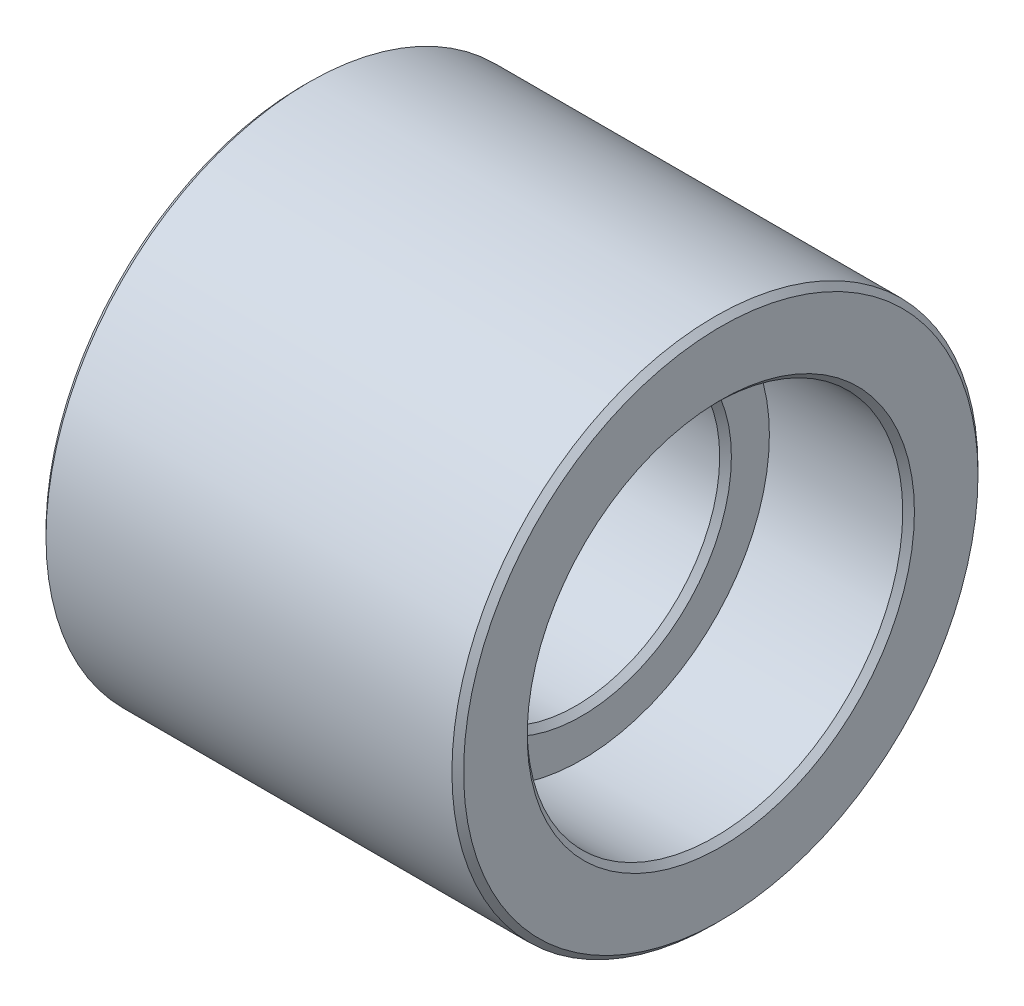
SolidWorks part; units mm, degrees
ref_plane "Front Plane" through (0, 0, 0) normal (0, 0, 1) x (1, 0, 0)
ref_plane "Top Plane" through (0, 0, 0) normal (0, 1, 0) x (1, 0, 0)
ref_plane "Right Plane" through (0, 0, 0) normal (1, 0, 0) x (0, 0, -1)
sketch "Sketch1" plane through (0, 0, 0) normal (0, 1, 0) x (1, 0, 0)
  line L0 (0, 9) -> (0, -9) construction
  line L1 (-7.1438, 9) -> (7.1438, 9)
  line L2 (7.1438, 9) -> (7.1438, 6.425)
  line L3 (7.1438, 6.425) -> (2.3813, 6.425)
  line L4 (2.3813, 6.425) -> (2.3813, 4.925)
  line L5 (2.3813, -6.425) -> (7.1438, -6.425)
  line L6 (7.1438, -6.425) -> (7.1438, -9)
  line L7 (7.1438, -9) -> (-7.1438, -9)
  line L8 (0, 0) -> (35.5203, 0) construction
  line L9 (2.3813, 4.925) -> (-2.3813, 4.925)
  line L10 (-7.1437, -6.425) -> (-7.1438, -9)
  line L11 (-2.3813, -4.925) -> (2.3813, -4.925)
  line L12 (2.3813, 4.925) -> (2.3813, 0) construction
  line L13 (2.3813, -4.925) -> (2.3813, -6.425)
  line L14 (2.3813, 0) -> (2.3813, -4.925) construction
  line L15 (-2.3813, -4.925) -> (-2.3812, -6.425)
  line L16 (-2.3812, -6.425) -> (-7.1437, -6.425)
  line L17 (-7.1438, 9) -> (-7.1437, 6.425)
  line L18 (-2.3812, 6.425) -> (-2.3813, 4.925)
  line L19 (-7.1437, 6.425) -> (-2.3812, 6.425)
  point P22 (0, -4.925)
  point P25 (0, 4.925)
  dimension "D1" = 4.7625
  dimension "D2" = 14.2875
  dimension "D3" = 1.5
  dimension "D4" = 12.85
  dimension "D5" = 18
revolve "Revolve1" add sketch "Sketch1" angle 360 about L8 region at (0, 0, -7.3812)
chamfer "Chamfer1" distance 0.2 angle 45 6 edges at (7.1438, 0, 9) (-7.1438, 0, 9) (-7.1437, 0, 6.425) (-2.3813, 0, 4.925) (2.3813, 0, 4.925) (7.1438, 0, 6.425)
